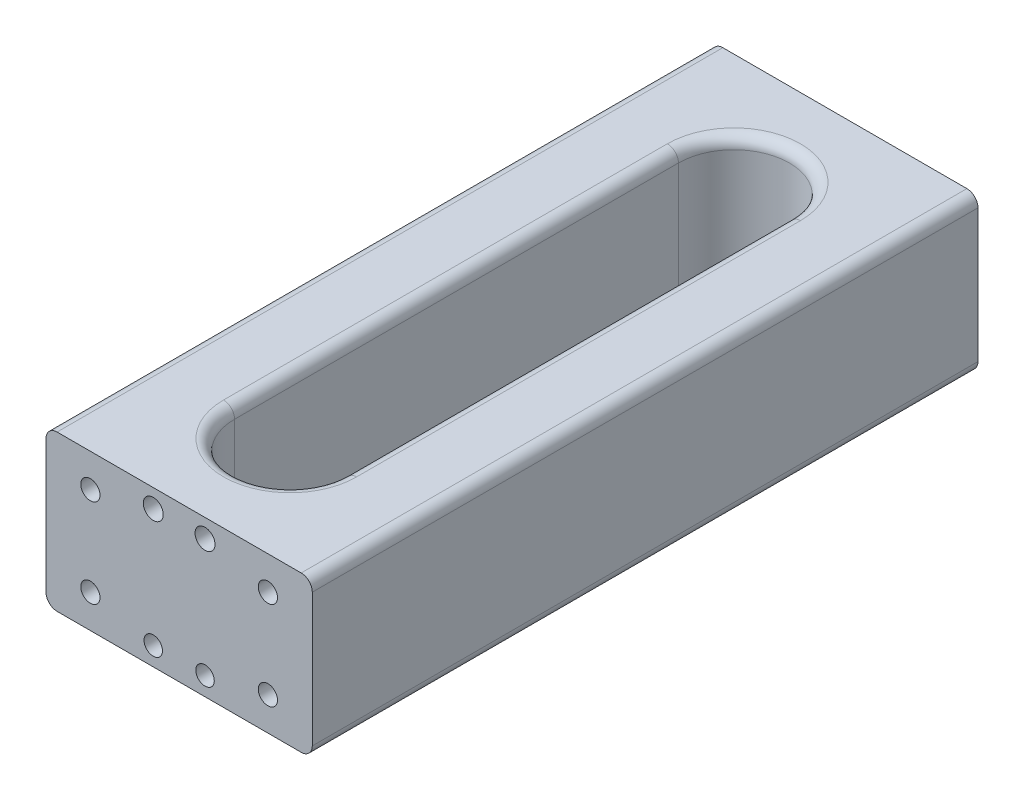
SolidWorks part; units mm, degrees
ref_plane "정면" through (0, 0, 0) normal (0, 0, 1) x (1, 0, 0)
ref_plane "윗면" through (0, 0, 0) normal (0, 1, 0) x (1, 0, 0)
ref_plane "우측면" through (0, 0, 0) normal (1, 0, 0) x (0, 0, -1)
sketch "스케치1" plane through (0, 0, 0) normal (0, 0, 1) x (1, 0, 0)
  line L0 (0, 10.5) -> (0, -10.5) construction
  line L1 (18, -10.5) -> (-18, -10.5)
  line L2 (18, -10.5) -> (18, 10.5)
  line L3 (18, 10.5) -> (-18, 10.5)
  line L4 (-18, -10.5) -> (-18, 10.5)
  line L5 (18, -10.5) -> (-18, 10.5) construction
  line L6 (18, 10.5) -> (-18, -10.5) construction
  line L7 (18, 0) -> (-18, 0) construction
  circle A0 centre (12, 6) radius 1.3
  circle A1 centre (-12, 6) radius 1.3
  circle A2 centre (12, -6) radius 1.3
  circle A3 centre (-12, -6) radius 1.3
  circle A4 centre (3.5, -8) radius 1.25
  circle A5 centre (-3.5, -8) radius 1.25
  circle A6 centre (3.5, 8) radius 1.35
  circle A7 centre (-3.5, 8) radius 1.35
  point P1 (0, 0)
extrude "보스-돌출1" add sketch "스케치1" along normal blind 90 contours A0 | A6 | A7 | A1 | A3 | A5 | A4 | A2 | L4 L1 L2 L3 A5 A4 A1 A0 A2 A3 A6 A7 region at (0, -0.0183, 0) region at (12, 6, 0) region at (-12, 6, 0) region at (12, -6, 0) region at (-12, -6, 0) region at (3.5, -8, 0) region at (-3.5, -8, 0) region at (3.5, 8, 0) region at (-3.5, 8, 0)
extrude "컷-돌출1" cut sketch "스케치1<5>" along normal blind 4 contours A0 | A6 | A7 | A1 | A3 | A5 | A4 | A2 region at (12, 6, 0) region at (-12, 6, 0) region at (-12, -6, 0) region at (3.5, 8, 0) region at (-3.5, 8, 0)
sketch "스케치1<5>" plane through (0, 0, 0) normal (0, 0, 1) x (1, 0, 0) same geometry as "스케치1"
extrude "컷-돌출2" cut sketch "스케치1<6>" against normal blind 4 from surface contours A6 | A0 | A7 | A1 | A3 | A5 | A4 | A2 region at (12, 6, 0) region at (-12, 6, 0) region at (12, -6, 0) region at (-12, -6, 0) region at (3.5, -8, 0) region at (-3.5, -8, 0) region at (3.5, 8, 0) region at (-3.5, 8, 0) starting at face at (0, 0, 90)
sketch "스케치1<6>" plane through (0, 0, 0) normal (0, 0, 1) x (1, 0, 0) same geometry as "스케치1"
sketch "스케치2" plane through (0, 10.5, 0) normal (0, 1, 0) x (1, 0, 0)
  line L0 (0, -15) -> (0, -75) construction
  line L1 (7.5, -15) -> (7.5, -75)
  line L2 (-7.5, -15) -> (-7.5, -75)
  line L3 (18, 0) -> (-18, 0) construction
  line L4 (18, -90) -> (-18, -90) construction
  arc A0 (7.5, -15) -> (-7.5, -15) centre (0, -15) ccw
  arc A1 (-7.5, -75) -> (7.5, -75) centre (0, -75) ccw
  point P3 (0, -45)
  dimension "D1" = 15
  dimension "D2" = 15
  dimension "D3" = 15
extrude "컷-돌출3" cut sketch "스케치2" against normal up to next
fillet "필렛1" radius 1.5 12 edges at (0, -10.5, 7.5) (7.5, -10.5, 45) (0, -10.5, 82.5) (0, 10.5, 82.5) (-7.5, 10.5, 45) (0, 10.5, 7.5) (-18, -10.5, 45) (-7.5, -10.5, 45) (18, -10.5, 45) (-18, 10.5, 45) (7.5, 10.5, 45) (18, 10.5, 45)
